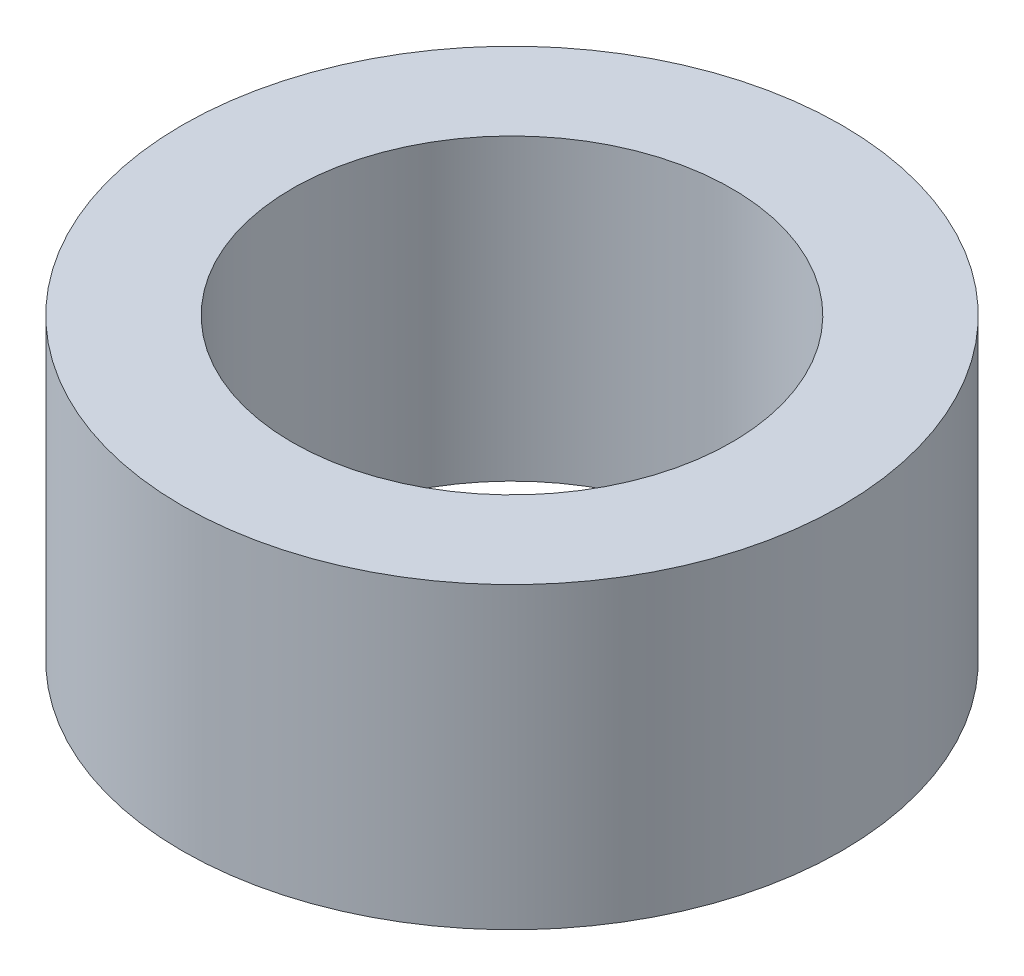
SolidWorks part; units mm, degrees
material "Nylon 101"
ref_plane "Front Plane" through (0, 0, 0) normal (0, 0, 1) x (1, 0, 0)
ref_plane "Top Plane" through (0, 0, 0) normal (0, 1, 0) x (1, 0, 0)
ref_plane "Right Plane" through (0, 0, 0) normal (1, 0, 0) x (0, 0, -1)
sketch "Sketch1" plane through (0, 0, 0) normal (0, 1, 0) x (1, 0, 0)
  circle A0 centre (0, 0) radius 3.175
  circle A1 centre (0, 0) radius 4.7625
  dimension "D1" = 6.35
  dimension "D2" = 9.525
extrude "Boss-Extrude1" add sketch "Sketch1" along normal blind 4.318
